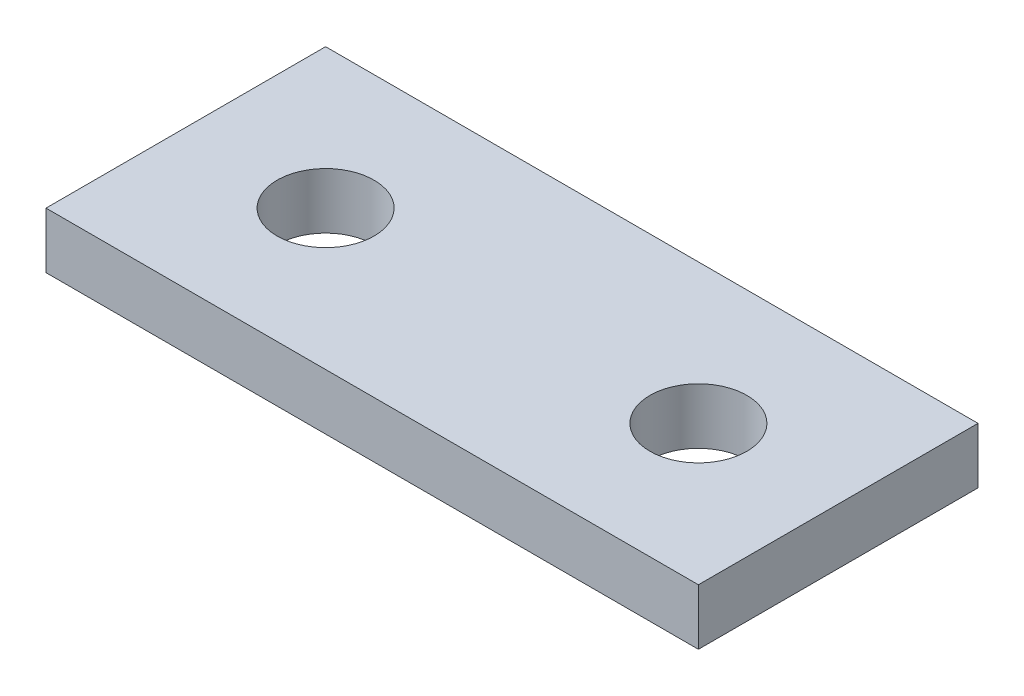
SolidWorks part; units mm, degrees
ref_plane "Спереди" through (0, 0, 0) normal (0, 0, 1) x (1, 0, 0)
ref_plane "Сверху" through (0, 0, 0) normal (0, 1, 0) x (1, 0, 0)
ref_plane "Справа" through (0, 0, 0) normal (1, 0, 0) x (0, 0, -1)
sketch "Эскиз1" plane through (0, 0, 0) normal (0, 1, 0) x (1, 0, 0)
  line L1 (-17.5, 7.5) -> (17.5, 7.5)
  line L2 (-17.5, 7.5) -> (-17.5, -7.5)
  line L3 (-17.5, -7.5) -> (17.5, -7.5)
  line L4 (17.5, 7.5) -> (17.5, -7.5)
  line L5 (-17.5, 7.5) -> (17.5, -7.5) construction
  line L6 (-17.5, -7.5) -> (17.5, 7.5) construction
  circle A1 centre (10, 0) radius 2.6
  circle A2 centre (-10, 0) radius 2.6
  point P0 (0, 0)
  point P6 (0, 0)
extrude "Бобышка-Вытянуть1" add sketch "Эскиз1" along normal blind 3
